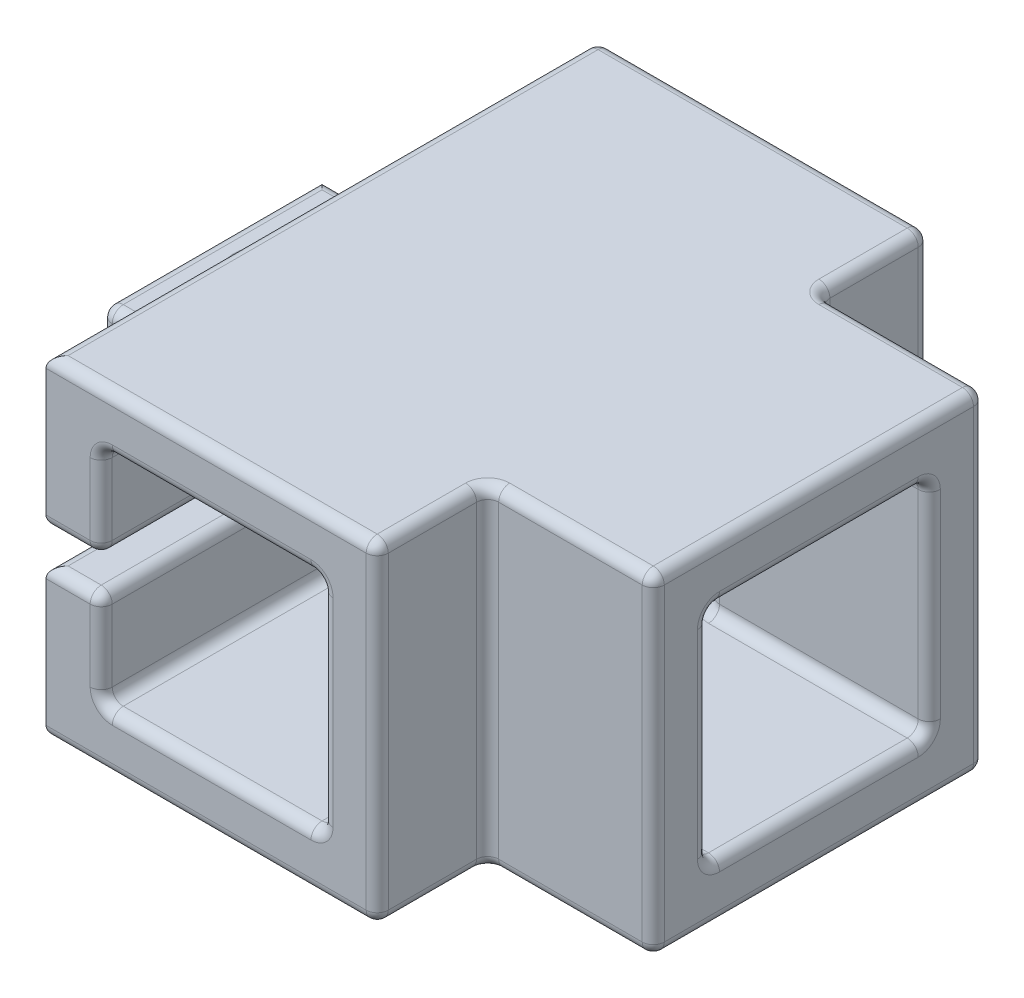
SolidWorks part; units mm, degrees
material "20% infill ABS"
ref_plane "Front Plane" through (0, 0, 0) normal (0, 0, 1) x (1, 0, 0)
ref_plane "Top Plane" through (0, 0, 0) normal (0, 1, 0) x (1, 0, 0)
ref_plane "Right Plane" through (0, 0, 0) normal (1, 0, 0) x (0, 0, -1)
sketch "Sketch1" plane through (0, 0, 0) normal (0, 0, 1) x (1, 0, 0)
  line L0 (-5.8424, 8.1021) -> (-5.8424, -11.8979)
  line L1 (-10.8424, 13.1021) -> (19.1576, 13.1021)
  line L2 (-10.8424, 13.1021) -> (-10.8424, -16.8979)
  line L3 (-10.8424, -16.8979) -> (19.1576, -16.8979)
  line L4 (19.1576, 13.1021) -> (19.1576, -16.8979)
  line L5 (-5.8424, -11.8979) -> (14.1576, -11.8979)
  line L6 (14.1576, 8.1021) -> (14.1576, -11.8979)
  line L7 (-5.8424, 8.1021) -> (14.1576, 8.1021)
  dimension "D1" = 30
  dimension "D2" = 30
  dimension "D3" = 5
extrude "Boss-Extrude1" add sketch "Sketch1" along normal blind 50
sketch "Sketch2" plane through (19.1576, 0, 0) normal (1, 0, 0) x (0, 0, -1)
  line L0 (-25, 13.1021) -> (-10, 13.1021)
  line L1 (-50, 13.1021) -> (0, 13.1021) construction
  line L2 (-10, 13.1021) -> (-10, -16.8979)
  line L3 (-50, -16.8979) -> (0, -16.8979) construction
  line L4 (-10, -16.8979) -> (-40, -16.8979)
  line L5 (-40, -16.8979) -> (-40, 13.1021)
  line L6 (-40, 13.1021) -> (-25, 13.1021)
  line L7 (-35, 8.1021) -> (-25, 8.1021)
  line L8 (-25, 8.1021) -> (-15, 8.1021)
  line L9 (-15, 8.1021) -> (-15, -11.8979)
  line L10 (-15, -11.8979) -> (-35, -11.8979)
  line L11 (-35, -11.8979) -> (-35, 8.1021)
  line L12 (-25, 13.1021) -> (-25, 8.1021) construction
  point P14 (0, 0)
  point P15 (0, 0)
  point P16 (0, 0)
  dimension "D1" = 5
  dimension "D2" = 20
  dimension "D3" = 5
  dimension "D4" = 5
  dimension "D5" = 5
extrude "Boss-Extrude2" add sketch "Sketch2" along normal blind 30 contours L6 L0 L2 L4 L5 | L7 L8 L9 L10 L11
sketch "Sketch3" plane through (19.1576, 0, 0) normal (1, 0, 0) x (0, 0, -1)
  line L0 (-35, 8.1021) -> (-15, 8.1021)
  line L1 (-15, 8.1021) -> (-15, -11.8979)
  line L2 (-15, -11.8979) -> (-35, -11.8979)
  line L3 (-35, -11.8979) -> (-35, 8.1021)
extrude "Cut-Extrude1" cut sketch "Sketch3" against normal blind 6
sketch "Sketch4" plane through (0, 0, 0) normal (0, 0, -1) x (-1, 0, 0)
  line L0 (5.8424, -11.8979) -> (5.8424, -1.8979)
  line L1 (5.8424, 8.1021) -> (5.8424, -11.8979) construction
  line L2 (5.8424, -1.8979) -> (5.8424, -0.3979)
  line L3 (5.8424, -0.3979) -> (10.8424, -0.3979)
  line L4 (10.8424, 13.1021) -> (10.8424, -16.8979) construction
  line L5 (10.8424, -0.3979) -> (20.8424, -0.3979)
  line L6 (20.8424, -0.3979) -> (20.8424, 4.6021)
  line L7 (20.8424, 4.6021) -> (10.8424, 4.6021)
  line L8 (10.8424, 4.6021) -> (10.8424, -0.3979)
  line L9 (10.8424, -0.3979) -> (10.8424, -3.3979)
  line L10 (10.8424, -3.3979) -> (20.8424, -3.3979)
  line L11 (20.8424, -3.3979) -> (20.8424, -8.3979)
  line L12 (20.8424, -8.3979) -> (10.8424, -8.3979)
  line L13 (10.8424, -8.3979) -> (10.8424, -3.3979)
  line M1 (10.8424, -16.8979) -> (10.8424, 13.1021)
extrude "Boss-Extrude3" add sketch "Sketch4" against normal blind 20 from offset 15 contours L6 L7 L5 M1 | L12 L11 L10 M1 region at (-15.8424, 2.1021, 0) region at (-15.8424, -5.8979, 0) offset against normal yes
sketch "Sketch5" plane through (0, 4.6021, 0) normal (0, 1, 0) x (1, 0, 0)
  line L0 (-20.8424, -15) -> (-10.8424, -35)
  circle A0 centre (-15.8424, -25) radius 2
extrude "Cut-Extrude2" cut sketch "Sketch5" against normal blind 30 contours L0 A0 | L0 A0 region at (-15.0832, 4.6021, 24.6204) region at (-16.6016, 4.6021, 25.3796)
sketch "Sketch6" plane through (0, 0, 50) normal (0, 0, 1) x (1, 0, 0)
  line L0 (-10.8424, -0.3979) -> (-5.8424, -0.3979)
  line L1 (-5.8424, 8.1021) -> (-5.8424, -11.8979) construction
  line L2 (-5.8424, -0.3979) -> (-5.8424, -3.3979)
  line L3 (-5.8424, -3.3979) -> (-10.8424, -3.3979)
  line L4 (-10.8424, 13.1021) -> (-10.8424, -16.8979) construction
  line L5 (-10.8424, -3.3979) -> (-10.8424, -0.3979)
extrude "Cut-Extrude3" cut sketch "Sketch6" against normal blind 140
sketch "Sketch7" plane through (49.1576, 0, 0) normal (1, 0, 0) x (0, 0, -1)
  line L1 (-10, 13.1021) -> (-40, 13.1021)
  line L2 (-10, 13.1021) -> (-10, -16.8979)
  line L3 (-10, -16.8979) -> (-40, -16.8979)
  line L4 (-40, 13.1021) -> (-40, -16.8979)
extrude "Cut-Extrude4" cut sketch "Sketch7" against normal blind 15
fillet "Fillet1" radius 1 54 edges at (-5.8424, -7.6479, 50) (-5.8424, -3.3979, 25) (24.1576, -11.8979, 35) (4.1576, -11.8979, 50) (-5.8424, -11.8979, 25) (24.1576, -11.8979, 15) (14.1576, -1.8979, 50) (14.1576, -11.8979, 42.5) (14.1576, -1.8979, 35) (14.1576, -11.8979, 7.5) (14.1576, -1.8979, 15) (24.1576, 8.1021, 15) (14.1576, 8.1021, 7.5) (4.1576, 8.1021, 50) (14.1576, 8.1021, 42.5) (24.1576, 8.1021, 35) (-5.8424, 3.8521, 50) (-5.8424, 8.1021, 25) (-5.8424, -0.3979, 25) (4.1576, 8.1021, 0) (14.1576, -1.8979, 0) (4.1576, -11.8979, 0) (-5.8424, -7.6479, 0) (-8.3424, -3.3979, 0) (-10.8424, -10.1479, 0) (-10.8424, 6.3521, 0) (-8.3424, -0.3979, 0) (-5.8424, 3.8521, 0) (19.1576, -1.8979, 0) (19.1576, -1.8979, 10) (34.1576, -1.8979, 35) (34.1576, -11.8979, 25) (34.1576, -1.8979, 15) (34.1576, 8.1021, 25) (34.1576, -1.8979, 10) (19.1576, -16.8979, 5) (4.1576, -16.8979, 0) (-10.8424, -16.8979, 25) (4.1576, -16.8979, 50) (34.1576, -16.8979, 25) (26.6576, -16.8979, 10) (26.6576, -16.8979, 40) (34.1576, -1.8979, 40) (19.1576, -1.8979, 50) (19.1576, -1.8979, 40) (19.1576, -16.8979, 45) (19.1576, 13.1021, 45) (4.1576, 13.1021, 50) (-10.8424, 13.1021, 25) (4.1576, 13.1021, 0) (19.1576, 13.1021, 5) (26.6576, 13.1021, 10) (34.1576, 13.1021, 25) (26.6576, 13.1021, 40)
fillet "Fillet2" radius 1 19 edges at (-10.8424, -5.8979, 35) (-10.5495, -3.6908, 0.2929) (-10.8424, -8.3979, 25) (-10.8424, -3.3979, 8) (-10.8424, 2.1021, 35) (-10.8424, 2.1021, 15) (-20.8424, -3.3979, 25) (-20.8424, -5.8979, 35) (-20.8424, -8.3979, 25) (-10.8424, -5.8979, 15) (-15.8424, -3.3979, 15) (-20.8424, -5.8979, 15) (-15.8424, -8.3979, 15) (-10.8424, 4.6021, 25) (-15.8424, 4.6021, 35) (-20.8424, 4.6021, 25) (-15.8424, 4.6021, 15) (-15.8424, 4.6021, 27) (-15.8424, -8.3979, 35)
fillet "Fillet3" radius 1 13 edges at (-20.5495, 4.3092, 34.7071) (-10.5495, -0.105, 0.2929) (-6.1353, -0.105, 49.7071) (-20.8424, 1.6021, 35) (-10.8424, -0.3979, 7.5) (-11.1353, -0.3979, 14.7071) (-16.3424, -0.3979, 15) (-20.8424, -0.3979, 25) (-16.3424, -0.3979, 35) (-11.1353, -0.3979, 35.2929) (-10.8424, -0.3979, 43) (-8.8424, -0.3979, 50) (-13.8424, -0.3979, 25)
fillet "Fillet4" radius 1 8 edges at (-6.1353, -3.6908, 49.7071) (-20.5495, -3.6908, 34.7071) (-15.8424, -3.3979, 23) (-8.8424, -3.3979, 50) (-10.8424, -3.3979, 43) (-11.1353, -3.3979, 35.2929) (-15.8424, -3.3979, 35) (-17.8424, -8.3979, 25)
